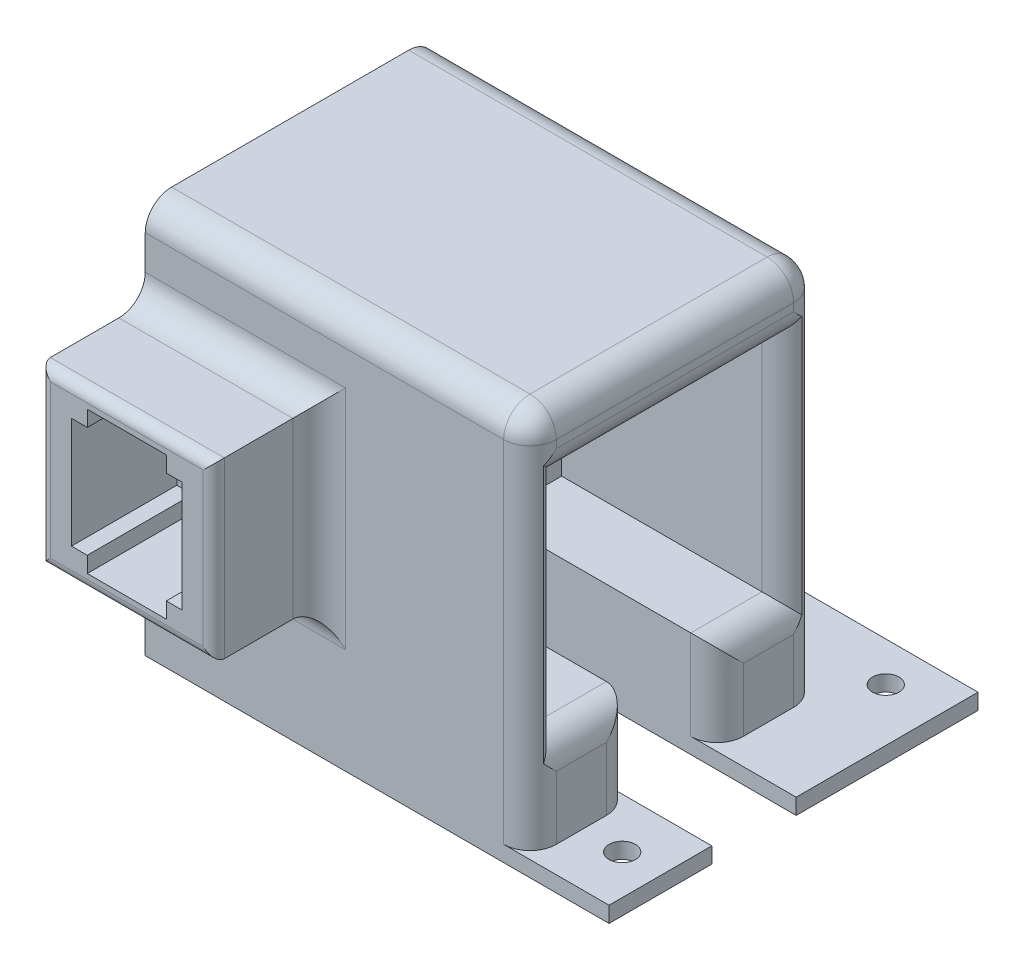
SolidWorks part; units mm, degrees
ref_plane "Alzado" through (0, 0, 0) normal (0, 0, 1) x (1, 0, 0)
ref_plane "Planta" through (0, 0, 0) normal (0, 1, 0) x (1, 0, 0)
ref_plane "Vista lateral" through (0, 0, 0) normal (1, 0, 0) x (0, 0, -1)
sketch "Sketch1" plane through (0, 0, 0) normal (0, 0, 1) x (1, 0, 0)
  line L1 (0, 0) -> (33, 0)
  line L2 (0, 0) -> (0, 33)
  line L3 (0, 33) -> (33, 33)
  line L4 (33, 0) -> (33, 33)
  dimension "D1" = 33
  dimension "D2" = 33
extrude "Boss-Extrude1" add sketch "Sketch1" along normal blind 20
shell "Shell1" thickness 6 removed face at (16.5, 16.5, 20)
sketch "Sketch2" plane through (0, 0, 0) normal (0, 0, -1) x (-1, 0, 0)
  line L1 (-33, 33) -> (0, 33) construction
  line L10 (-73, -22) -> (0, -22)
  line L11 (-73, -22) -> (-73, 49.5)
  line L12 (-73, 49.5) -> (0, 49.5)
  line L13 (0, -22) -> (0, 49.5)
  line L15 (0, 33) -> (0, 0) construction
  dimension "D1" = 71.5
  dimension "D2" = 16.5
  dimension "D3" = 73
extrude "Boss-Extrude2" add sketch "Sketch2" along normal blind 55
ref_plane "Plane25" through (16.5, 0, 0) normal (-1, 0, 0) x (0, 0, 1)
sketch "Sketch7" plane through (0, 27, 0) normal (0, -1, 0) x (1, 0, 0)
  line L0 (27, 20) -> (6, 20) construction
  line L1 (9, 20) -> (24, 20)
  line L2 (9, 20) -> (9, -30)
  line L3 (9, -30) -> (24, -30)
  line L4 (24, 20) -> (24, -30)
  line L6 (0, 20) -> (0, 0) construction
  dimension "D1" = 15
  dimension "D2" = 9
  dimension "D3" = 50
extrude "Cut-Extrude2" cut sketch "Sketch7" against normal blind 3
ref_plane "Plane26" through (0, 16.5, 0) normal (0, -1, 0) x (-1, 0, 0)
sketch "Sketch9" plane through (0, 0, 6) normal (0, 0, 1) x (1, 0, 0)
  line L1 (6, 27) -> (27, 27)
  line L2 (6, 27) -> (6, 6)
  line L3 (6, 6) -> (27, 6)
  line L4 (27, 27) -> (27, 6)
extrude "Cut-Extrude5" cut sketch "Sketch9" against normal blind 45 contours L2 L1 L4 L3
mirror "Mirror2" about plane through (0, 16.5, 0) normal (0, -1, 0) of "Cut-Extrude2"
sketch "Sketch16" plane through (33, 0, 0) normal (1, 0, 0) x (0, 0, -1)
  line L0 (0, 16.5) -> (55, 16.5) construction
  line L1 (-11, 16.5) -> (11, 16.5) construction
  line L4 (0, -11) -> (55, -11)
  line L5 (0, -11) -> (0, 44)
  line L6 (0, 44) -> (55, 44)
  line L7 (55, -11) -> (55, 44)
  line L8 (0, -11) -> (55, 44) construction
  line L9 (0, 44) -> (55, -11) construction
  line L11 (0, -22) -> (0, 49.5) construction
  point P6 (27.5, 16.5)
  dimension "D1" = 55
  dimension "D2" = 55
extrude "Boss-Extrude5" add sketch "Sketch16" along normal blind 40
shell "Shell8" [suppressed] thickness 3
sketch "Sketch17" [suppressed] plane through (30, 0, 0) normal (1, 0, 0) x (0, 0, -1)
  line L1 (9.4106, 28.1579) -> (46.608, 28.1579)
  line L2 (9.4106, 28.1579) -> (9.4106, 5.2023)
  line L3 (9.4106, 5.2023) -> (46.608, 5.2023)
  line L4 (46.608, 28.1579) -> (46.608, 5.2023)
extrude "Cut-Extrude9" [suppressed] cut sketch "Sketch17" against normal blind 17
sketch "Sketch18" [suppressed] plane through (0, 0, -39) normal (0, 0, 1) x (1, 0, 0)
  line L0 (27, 27) -> (27, 6) construction
  line L1 (6, 27) -> (27, 27)
  line L2 (6, 27) -> (6, 16.5)
  line L3 (6, 16.5) -> (27, 16.5)
  line L4 (27, 27) -> (27, 16.5)
extrude "Cut-Extrude10" [suppressed] cut sketch "Sketch18" against normal blind 10
sketch "Sketch19" [suppressed] plane through (0, -8, 0) normal (0, 1, 0) x (1, 0, 0)
  line L0 (73, 55) -> (73, 0) construction
  line L1 (73, 38.5) -> (61, 38.5)
  line L2 (73, 38.5) -> (73, 16.5)
  line L3 (73, 16.5) -> (61, 16.5)
  line L4 (61, 38.5) -> (61, 16.5)
  line L6 (73, 3) -> (30, 3) construction
  dimension "D1" = 22
  dimension "D2" = 13.5
  dimension "D3" = 12
extrude "Cut-Extrude11" [suppressed] cut sketch "Sketch19" against normal blind 10
sketch "Sketch20" [suppressed] plane through (0, 0, 20) normal (0, 0, 1) x (1, 0, 0)
  line L0 (27, 6) -> (27, 27) construction
  line L1 (27, 28.948) -> (33, 28.948)
  line L2 (27, 28.948) -> (27, 3.948)
  line L3 (27, 3.948) -> (33, 3.948)
  line L4 (33, 28.948) -> (33, 3.948)
  line L5 (33, 33) -> (33, 0) construction
  dimension "D1" = 25
extrude "Cut-Extrude12" [suppressed] cut sketch "Sketch20" against normal blind 15
sketch "Sketch21" [suppressed] plane through (6, 0, 0) normal (1, 0, 0) x (0, 0, -1)
  line L1 (9.523, 27.9555) -> (42, 27.9555)
  line L2 (9.523, 27.9555) -> (9.523, 5.2023)
  line L3 (9.523, 5.2023) -> (42, 5.2023)
  line L4 (42, 27.9555) -> (42, 5.2023)
extrude "Cut-Extrude13" [suppressed] cut sketch "Sketch21" against normal blind 10
sketch "Sketch22" plane through (73, 0, 0) normal (1, 0, 0) x (0, 0, -1)
  line L1 (6, -5) -> (19.5, -5)
  line L2 (6, -5) -> (6, 38)
  line L3 (6, 38) -> (49, 38)
  line L4 (49, -5) -> (49, 38)
  line L5 (6, -5) -> (49, 38) construction
  line L6 (6, 38) -> (49, -5) construction
  line L8 (19.5, -5) -> (19.5, -22)
  line L9 (19.5, -22) -> (35.5, -22)
  line L10 (35.5, -5) -> (35.5, -22)
  line L11 (35.5, -5) -> (49, -5)
  line L14 (0, -22) -> (0, 49.5) construction
  line L15 (55, 49.5) -> (0, 49.5) construction
  line L16 (55, -22) -> (0, -22) construction
  point P0 (27.5, 16.5)
  point P9 (27.5, -22)
  dimension "D1" = 43
  dimension "D2" = 43
  dimension "D3" = 16
  dimension "D4" = 11.5
  dimension "D5" = 6
extrude "Cut-Extrude14" cut sketch "Sketch22" against normal up to surface (67 mm away) up to face at (6, 16.5, -9.5)
sketch "Sketch23" plane through (0, 0, 20) normal (0, 0, 1) x (1, 0, 0)
  line L0 (9, 3) -> (9, 6) construction
  line L1 (6, 6) -> (9, 6)
  line L2 (6, 6) -> (6, 9)
  line L3 (6, 9) -> (9, 9)
  line L4 (9, 6) -> (9, 9)
  line L5 (6, 27) -> (9, 27)
  line L6 (6, 27) -> (6, 24)
  line L7 (6, 24) -> (9, 24)
  line L8 (9, 27) -> (9, 24)
  line L9 (27, 27) -> (24, 27)
  line L10 (27, 27) -> (27, 24)
  line L11 (27, 24) -> (24, 24)
  line L12 (24, 27) -> (24, 24)
  line L13 (27, 6) -> (24, 6)
  line L14 (27, 6) -> (27, 9)
  line L15 (27, 9) -> (24, 9)
  line L16 (24, 6) -> (24, 9)
  line L17 (24, 3) -> (24, 6) construction
  line L18 (24, 30) -> (24, 27) construction
  line L19 (9, 30) -> (9, 27) construction
  dimension "D1" = 3
  dimension "D2" = 3
  dimension "D3" = 3
  dimension "D4" = 3
extrude "Boss-Extrude6" add sketch "Sketch23" along normal blind 6 from surface at -26 starting at face at (22.25, 16.5, -6)
sketch "Sketch24" plane through (73, 0, 0) normal (1, 0, 0) x (0, 0, -1)
  line L0 (49, 38) -> (49, -5) construction
  line L1 (6, -5) -> (19.5, -5)
  line L2 (6, -5) -> (6, 0)
  line L3 (6, 0) -> (19.5, 0)
  line L4 (19.5, -5) -> (19.5, 0)
  line L5 (35.5, -5) -> (49, -5)
  line L6 (35.5, -5) -> (35.5, 0)
  line L7 (35.5, 0) -> (49, 0)
  line L8 (49, -5) -> (49, 0)
  line L10 (19.5, -5) -> (19.5, -22) construction
  dimension "D1" = 5
extrude "Boss-Extrude7" add sketch "Sketch24" against normal up to surface (24 mm away) from offset 43 offset against normal yes
sketch "Sketch25" plane through (0, -22, 0) normal (0, -1, 0) x (1, 0, 0)
  line L0 (73, -55) -> (0, -55) construction
  line L1 (0, 0) -> (88, 0)
  line L2 (0, 0) -> (0, -70)
  line L3 (0, -70) -> (88, -70)
  line L4 (88, 0) -> (88, -19.5)
  line L5 (73, -19.5) -> (73, 0) construction
  line L6 (88, -19.5) -> (30, -19.5)
  line L7 (30, -19.5) -> (30, -35.5)
  line L8 (30, -35.5) -> (88, -35.5)
  line L9 (6, -19.5) -> (73, -19.5) construction
  line L10 (6, -35.5) -> (73, -35.5) construction
  line L11 (88, -35.5) -> (88, -70)
  circle A0 centre (10, -62.5) radius 2.5
  circle A1 centre (78, -62.5) radius 2.5
  circle A2 centre (80.5, -10) radius 2.5
  dimension "D4" = 5
  dimension "D5" = 5
  dimension "D6" = 5
  dimension "D1" = 15
  dimension "D2" = 15
  dimension "D3" = 58
  dimension "D7" = 10
  dimension "D8" = 7.5
  dimension "D9" = 7.5
  dimension "D10" = 10
  dimension "D11" = 7.5
  dimension "D12" = 10
extrude "Boss-Extrude8" add sketch "Sketch25" along normal blind 3
fillet "Fillet1" radius 5 15 edges at (16.5, 0, 0) (33, 16.5, 0) (16.5, 33, 0) (36.5, 49.5, 0) (36.5, 49.5, -55) (73, -13.5, -35.5) (73, -13.5, -19.5) (73, -5, -42.25) (73, -5, -12.75) (73, 16.5, -49) (73, 38, -27.5) (73, 16.5, -6) (73, 13.75, -55) (73, 13.75, 0) (73, 49.5, -27.5)
fillet "Fillet2" radius 2 4 edges at (33, 16.5, 20) (16.5, 0, 20) (0, 16.5, 20) (16.5, 33, 20)
